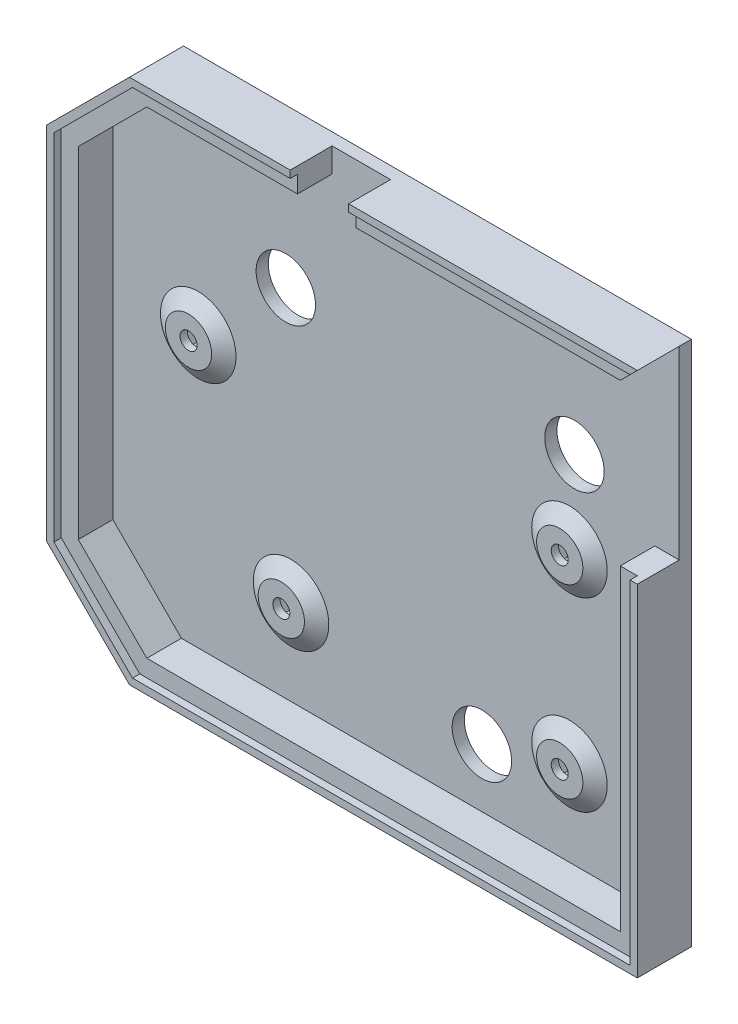
SolidWorks part; units mm, degrees
material "Delrin 2700 NC010, copolymère d'acétal à faible viscosité (SS)"
ref_plane "Plan de face" through (0, 0, 0) normal (0, 0, 1) x (1, 0, 0)
ref_plane "Plan de dessus" through (0, 0, 0) normal (0, 1, 0) x (1, 0, 0)
ref_plane "Plan de droite" through (0, 0, 0) normal (1, 0, 0) x (0, 0, -1)
sketch "Esquisse1" plane through (0, 0, 0) normal (0, 0, 1) x (1, 0, 0)
  line L0 (0, -85) -> (17, -102)
  line L4 (121.25, 6) -> (121.25, -102)
  line L5 (17, 6) -> (0, -11)
  line L7 (121.25, 6) -> (17, 6)
  line L8 (0, -11) -> (0, -85)
  line L9 (17, -102) -> (121.25, -102)
  dimension "D1" = 108
  dimension "D2" = 121.25
  dimension "D3" = 17
  dimension "D4" = 17
  dimension "D5" = 17
  dimension "D6" = 17
extrude "Boss.-Extru.1" add sketch "Esquisse1" along normal blind 2.5
sketch "Esquisse2" plane through (0, 0, 2.5) normal (0, 0, 1) x (1, 0, 0)
  line L0 (0, -11) -> (0, -85) construction
  line L1 (5, 1) -> (116.25, 1) construction
  line L2 (5, 1) -> (5, -97) construction
  line L3 (5, -97) -> (116.25, -97) construction
  line L4 (116.25, 1) -> (116.25, -97) construction
  line L5 (17, -102) -> (121.25, -102) construction
  line L6 (121.25, -102) -> (121.25, 6) construction
  line L7 (121.25, 6) -> (17, 6) construction
  line L8 (116.25, -32) -> (121.25, -32)
  line L9 (5, -82.9289) -> (19.0711, -97)
  line L10 (0, -85) -> (17, -102) construction
  line L11 (5, -13.0711) -> (19.0711, 1)
  line L12 (17, 6) -> (0, -11) construction
  line L14 (5, -13.0711) -> (5, -82.9289)
  line L15 (19.0711, -97) -> (116.25, -97)
  line L16 (121.25, 6) -> (121.25, -102) construction
  line L17 (121.25, -102) -> (17, -102)
  line L18 (17, -102) -> (0, -85)
  line L19 (0, -85) -> (0, -11)
  line L20 (0, -11) -> (17, 6)
  line L22 (116.25, 1) -> (121.25, 6)
  line L23 (116.25, -97) -> (116.25, -32)
  line L24 (121.25, -32) -> (121.25, -102)
  line L25 (50, 1) -> (50, 6)
  line L26 (62, 1) -> (62, 6)
  line L27 (19.0711, 1) -> (50, 1)
  line L28 (50, 6) -> (17, 6)
  line L29 (62, 6) -> (121.25, 6)
  line L30 (116.25, 1) -> (62, 1)
  point P33 (50, 1)
  point P34 (62, 1)
  dimension "D1" = 5
  dimension "D2" = 5
  dimension "D3" = 5
  dimension "D4" = 5
  dimension "D5" = 5
  dimension "D6" = 5
  dimension "D7" = 70
  dimension "D8" = 45
  dimension "D9" = 12
extrude "Boss.-Extru.2" add sketch "Esquisse2" along normal blind 8.6
sketch "Esquisse3" plane through (0, 0, 2.5) normal (0, 0, 1) x (1, 0, 0)
  line L0 (116.25, -32) -> (116.25, -97) construction
  line L2 (5, -82.9289) -> (5, -13.0711) construction
  line L3 (116.25, -32) -> (116.25, -97) construction
  line L4 (116.25, -97) -> (19.0711, -97) construction
  line L5 (62, 6) -> (50, 6) construction
  circle A0 centre (99.75, -24) radius 6.1
  circle A1 centre (40.5, -24) radius 6.1
  circle A2 centre (80.75, -85) radius 6.1
  dimension "D1" = 16.5
  dimension "D2" = 30
  dimension "D3" = 30
  dimension "D4" = 35.5
  dimension "D5" = 35.5
  dimension "D6" = 12
extrude "Enlèv. mat.-Extru.1" cut sketch "Esquisse3" against normal blind 10
sketch "Esquisse5" plane through (0, 0, 2.5) normal (0, 0, 1) x (1, 0, 0)
  line L0 (116.25, -97) -> (19.0711, -97) construction
  line L1 (116.25, -32) -> (116.25, -97) construction
  point P0 (22.525, -41.37)
  point P1 (98.725, -41.37)
  point P2 (98.725, -79.47)
  point P3 (41.575, -79.47)
  dimension "D1" = 38.1
  dimension "D2" = 17.53
  dimension "D3" = 17.525
  dimension "D4" = 76.2
  dimension "D5" = 57.15
ref_axis "Axe5" through (22.525, -41.37, 2.5) along (0, 0, 1)
ref_axis "Axe6" through (98.725, -41.37, 2.5) along (0, 0, 1)
ref_axis "Axe7" through (41.575, -79.47, 2.5) along (0, 0, 1)
ref_axis "Axe8" through (98.725, -79.47, 2.5) along (0, 0, 1)
sketch3d "Esquisse3D5"
  line L0 (22.525, -41.37, 2.5) -> (98.725, -41.37, 2.5) construction
  line L1 (41.575, -79.47, 2.5) -> (98.725, -79.47, 2.5) construction
ref_plane "Plan4" through (98.725, -41.37, 2.5) normal (1, 0, 0) x (0, 0, -1)
sketch "Esquisse8" plane through (98.725, -41.37, 2.5) normal (1, 0, 0) x (0, 0, -1)
  line L0 (0, 1.75) -> (0, 7.75)
  line L1 (0, 7.75) -> (-2, 4.75)
  line L2 (-2, 4.75) -> (-2, 1.75)
  line L3 (-2, 1.75) -> (0, 1.75)
  line L5 (0, 0) -> (-50.5083, 0) construction
  point P0 (0, 1.75)
  dimension "D1" = 6
  dimension "D2" = 3
  dimension "D3" = 2
  dimension "D4" = 1.75
revolve "Révolution3" add sketch "Esquisse8" angle 360 about axis through (98.725, -41.37, 2.5) along (0, 0, 1)
ref_plane "Plan5" through (41.575, -79.47, 2.5) normal (1, 0, 0) x (0, 0, -1)
sketch "Esquisse9" plane through (41.575, -79.47, 2.5) normal (1, 0, 0) x (0, 0, -1)
  line L0 (0, 1.75) -> (0, 7.75)
  line L1 (0, 7.75) -> (-2, 4.75)
  line L2 (-2, 4.75) -> (-2, 1.75)
  line L3 (-2, 1.75) -> (0, 1.75)
  point P0 (0, 1.75)
  dimension "D1" = 2
  dimension "D2" = 6
  dimension "D3" = 3
  dimension "D4" = 1.75
revolve "Révolution4" add sketch "Esquisse9" angle 360 about axis through (41.575, -79.47, 2.5) along (0, 0, 1)
ref_plane "Plan6" through (98.725, -79.47, 2.5) normal (1, 0, 0) x (0, 0, -1)
sketch "Esquisse10" plane through (98.725, -79.47, 2.5) normal (1, 0, 0) x (0, 0, -1)
  line L0 (0, 1.75) -> (0, 7.75)
  line L1 (0, 7.75) -> (-2, 4.75)
  line L2 (-2, 4.75) -> (-2, 1.75)
  line L3 (-2, 1.75) -> (0, 1.75)
  point P0 (0, 1.75)
  dimension "D1" = 6
  dimension "D2" = 2
  dimension "D3" = 3
  dimension "D4" = 1.75
revolve "Révolution5" add sketch "Esquisse10" angle 360 about axis through (98.725, -79.47, 2.5) along (0, 0, 1)
hole_wizard "Dégagement M32" positions "Esquisse15" profile "Esquisse16" hole size "M3" standard "Ansi Metric" end condition up to next
sketch "Esquisse15" plane through (0, 0, 2.5) normal (0, 0, 1) x (1, 0, 0)
  point P0 (22.525, -41.37)
  point P3 (41.575, -79.47)
  point P6 (98.725, -41.37)
  point P9 (98.725, -79.47)
sketch "Esquisse16" plane through (22.525, -41.37, 2.5) normal (1, 0, 0) x (0, -1, 0)
  line L0 (0, 0) -> (0, 2.5)
  line L1 (0, 2.5) -> (1.8, 2.5)
  line L2 (1.8, 2.5) -> (1.8, 0)
  line L5 (1.8, 0) -> (0, 0)
  line L11 (0, -6.35) -> (0, 107.95) construction
  dimension "Diamètre du perçage jusqu'au prochain" = 3.6
  dimension "Profondeur du perçage jusqu'au prochain" = 2.5
ref_plane "Plan7" through (22.525, -41.37, 2.5) normal (1, 0, 0) x (0, 0, -1)
sketch "Esquisse17" plane through (22.525, -41.37, 2.5) normal (1, 0, 0) x (0, 0, -1)
  line L1 (0, 1.75) -> (0, 7.75)
  line L2 (0, 7.75) -> (-2, 4.75)
  line L3 (-2, 4.75) -> (-2, 1.75)
  line L4 (-2, 1.75) -> (0, 1.75)
  line L5 (0, 0) -> (-51.2543, 0) construction
  dimension "D1" = 1.75
  dimension "D2" = 6
  dimension "D3" = 3
  dimension "D4" = 2
revolve "Révolution6" add sketch "Esquisse17" angle 360 about axis through (22.525, -41.37, 2.5) along (0, 0, 1)
ref_point "Point1"
ref_point "Point2"
ref_point "Point3"
ref_point "Point4"
sketch "Esquisse18" plane through (0, 0, 0) normal (0, 0, -1) x (-1, 0, 0)
  line L1 (-97.1662, -76.77) -> (-100.2838, -76.77)
  line L2 (-100.2838, -76.77) -> (-101.8427, -79.47)
  line L3 (-101.8427, -79.47) -> (-100.2838, -82.17)
  line L4 (-100.2838, -82.17) -> (-97.1662, -82.17)
  line L5 (-97.1662, -82.17) -> (-95.6073, -79.47)
  line L6 (-95.6073, -79.47) -> (-97.1662, -76.77)
  line L7 (-97.1662, -38.67) -> (-100.2838, -38.67)
  line L8 (-100.2838, -38.67) -> (-101.8427, -41.37)
  line L9 (-101.8427, -41.37) -> (-100.2838, -44.07)
  line L10 (-100.2838, -44.07) -> (-97.1662, -44.07)
  line L11 (-97.1662, -44.07) -> (-95.6073, -41.37)
  line L12 (-95.6073, -41.37) -> (-97.1662, -38.67)
  line L13 (-19.4073, -41.37) -> (-20.9662, -38.67)
  line L14 (-20.9662, -38.67) -> (-24.0838, -38.67)
  line L15 (-24.0838, -38.67) -> (-25.6427, -41.37)
  line L16 (-25.6427, -41.37) -> (-24.0838, -44.07)
  line L17 (-24.0838, -44.07) -> (-20.9662, -44.07)
  line L18 (-20.9662, -44.07) -> (-19.4073, -41.37)
  line L19 (-38.4573, -79.47) -> (-40.0162, -76.77)
  line L20 (-40.0162, -76.77) -> (-43.1338, -76.77)
  line L21 (-43.1338, -76.77) -> (-44.6927, -79.47)
  line L22 (-44.6927, -79.47) -> (-43.1338, -82.17)
  line L23 (-43.1338, -82.17) -> (-40.0162, -82.17)
  line L24 (-40.0162, -82.17) -> (-38.4573, -79.47)
  line L26 (-17, -102) -> (-121.25, -102) construction
  circle A0 centre (-98.725, -79.47) radius 2.7 construction
  circle A1 centre (-98.725, -41.37) radius 2.7 construction
  circle A2 centre (-22.525, -41.37) radius 2.7 construction
  circle A3 centre (-41.575, -79.47) radius 2.7 construction
  dimension "D1" = 5.4
  dimension "D2" = 5.4
  dimension "D3" = 5.4
  dimension "D4" = 5.4
extrude "Enlèv. mat.-Extru.2" cut sketch "Esquisse18" against normal blind 3
sketch "Esquisse20" plane through (0, 0, 11.1) normal (0, 0, 1) x (1, 0, 0)
  line L0 (17, 6) -> (19.0711, 1) construction
  line L1 (5, -13.0711) -> (0, -11) construction
  line L2 (5, -82.9289) -> (0, -85) construction
  line L3 (17, -102) -> (19.0711, -97) construction
  line L4 (116.25, -97) -> (121.25, -102) construction
  line L5 (121.25, 6) -> (116.25, 1) construction
  line L12 (121.25, 6) -> (62, 6) construction
  line L13 (1.5, 4.5) -> (119.75, 4.5) construction
  line L14 (1.5, 4.5) -> (1.5, -100.5) construction
  line L15 (1.5, -100.5) -> (119.75, -100.5) construction
  line L16 (119.75, 4.5) -> (119.75, -100.5) construction
  line L17 (121.25, -32) -> (121.25, 6) construction
  line L18 (17, -102) -> (121.25, -102) construction
  line L19 (0, -11) -> (0, -85) construction
  line L20 (119.75, 4.5) -> (17.6213, 4.5)
  line L21 (17.6213, 4.5) -> (1.5, -11.6213)
  line L22 (1.5, -11.6213) -> (1.5, -84.3787)
  line L23 (1.5, -84.3787) -> (17.6213, -100.5)
  line L24 (17.6213, -100.5) -> (119.75, -100.5)
  line L25 (119.75, -100.5) -> (119.75, 4.5)
  dimension "D1" = 1.5
  dimension "D2" = 1.5
  dimension "D3" = 1.5
  dimension "D4" = 1.5
extrude "Enlèv. mat.-Extru.3" cut sketch "Esquisse20" against normal blind 1.5
